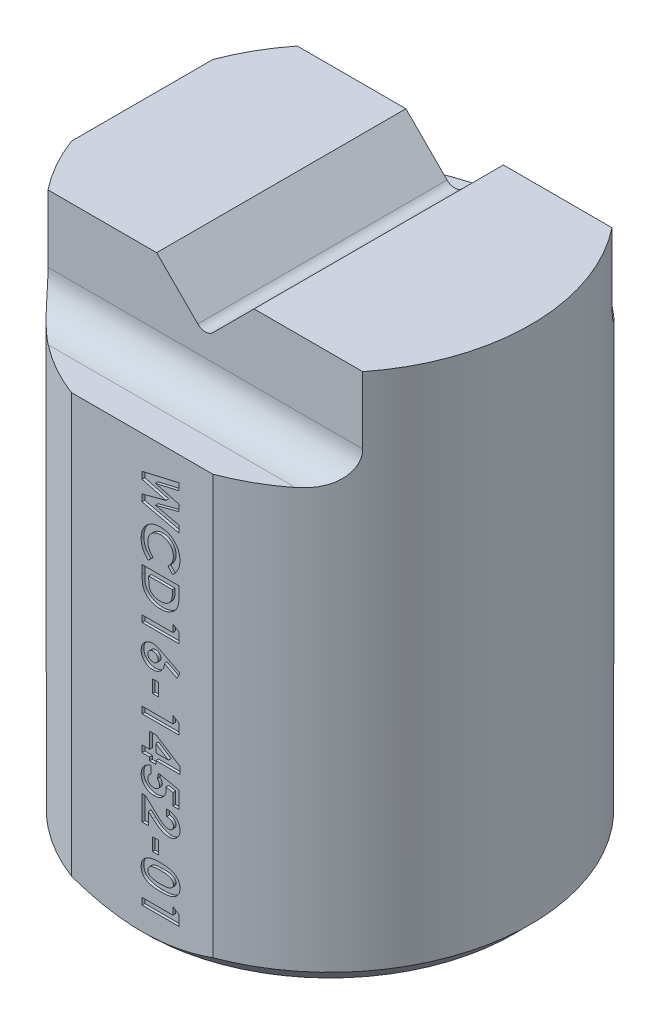
SolidWorks part; units mm, degrees
material "S7"
ref_plane "Alzado" through (0, 0, 0) normal (0, 0, 1) x (1, 0, 0)
ref_plane "Planta" through (0, 0, 0) normal (0, 1, 0) x (1, 0, 0)
ref_plane "Vista lateral" through (0, 0, 0) normal (1, 0, 0) x (0, 0, -1)
sketch "Croquis1" plane through (0, 0, 0) normal (0, 1, 0) x (1, 0, 0)
  line L0 (-17.8054, 6.701) -> (-17.8054, -6.701)
  line L1 (-6.701, -17.8054) -> (6.701, -17.8054)
  arc A0 (-17.8054, -6.701) -> (-6.701, -17.8054) centre (0, 0) ccw
  arc A1 (6.701, -17.8054) -> (-17.8054, 6.701) centre (0, 0) ccw
  dimension "D3" = 38.0492
  dimension "D1" = 36.83
  dimension "D2" = 36.83
extrude "Saliente-Extruir1" add sketch "Croquis1" along normal blind 50.8
sketch "Croquis2" plane through (-17.8054, 0, 0) normal (1, 0, 0) x (0, 0, -1)
  line L0 (0, 50.8) -> (0, 0) construction
  line L20 (11.811, 50.8) -> (11.811, 44.45)
  line L21 (19.0246, 50.8) -> (-17.8054, 50.8) construction
  line L22 (14.986, 41.275) -> (19.0246, 41.275)
  line L23 (19.0246, 41.275) -> (19.0246, 50.8)
  line L24 (19.0246, 50.8) -> (11.811, 50.8)
  line L26 (-19.0246, 50.8) -> (-11.811, 50.8)
  line L27 (-19.0246, 41.275) -> (-19.0246, 50.8)
  line L28 (-14.986, 41.275) -> (-19.0246, 41.275)
  line L29 (-11.811, 50.8) -> (-11.811, 44.45)
  arc A2 (11.811, 44.45) -> (14.986, 41.275) centre (14.986, 44.45) ccw
  arc A3 (-11.811, 44.45) -> (-14.986, 41.275) centre (-14.986, 44.45) cw
  dimension "D1" = 9.525
  dimension "D2" = 3.175
  dimension "D3" = 23.622
extrude "Cortar-Extruir1" cut sketch "Croquis2" along normal through all
sketch "Croquis3" plane through (0, 0, 11.811) normal (0, 0, 1) x (1, 0, 0)
  line L0 (-14.9143, 50.8) -> (14.9143, 50.8) construction
  line L1 (-4.6159, 50.8) -> (-0.7184, 46.9026)
  line L2 (0.7184, 46.9026) -> (4.6159, 50.8)
  line L3 (4.6159, 50.8) -> (-4.6159, 50.8)
  line L4 (0, 47.621) -> (0, 50.8) construction
  circle A0 centre (0, 50.8) radius 3.2639 construction
  arc A1 (-0.7184, 46.9026) -> (0.7184, 46.9026) centre (0, 47.621) ccw
  dimension "D1" = 6.5278
  dimension "D3" = 1.016
  dimension "D2" = 90
extrude "Cortar-Extruir2" cut sketch "Croquis3" against normal through all
chamfer "Chaflán1" distance 1.5875 angle 45 1 edges at (13.4524, 0, -13.4524)
sketch "Croquis4" plane through (0, 0, 17.8054) normal (0, 0, 1) x (1, 0, 0)
  line L0 (0, 41.275) -> (0, 0) construction
  line L1 (-6.701, 41.275) -> (6.701, 41.275) construction
  text T0 "<b>WCD16-1452-01</b>"
extrude "Cortar-Extruir3" cut sketch "Croquis4" against normal blind 0.254
